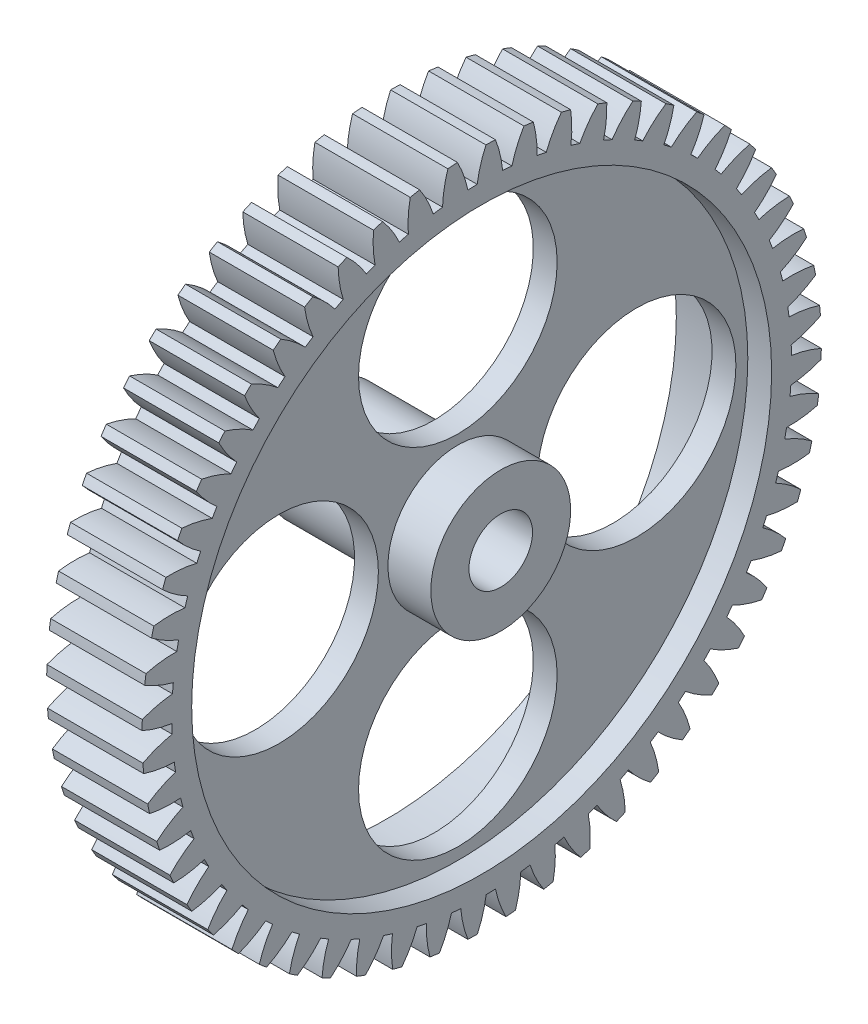
SolidWorks part; units mm, degrees
ref_plane "Front Plane" through (0, 0, 0) normal (0, 0, 1) x (1, 0, 0)
ref_plane "Top Plane" through (0, 0, 0) normal (0, 1, 0) x (1, 0, 0)
ref_plane "Right Plane" through (0, 0, 0) normal (1, 0, 0) x (0, 0, -1)
sketch "Sketch1" plane through (0, 0, 0) normal (1, 0, 0) x (0, 0, -1)
  line L0 (0, 0) -> (0.1063, 3.9986) construction
  line L1 (1.0369, 38.9862) -> (1.1366, 42.7349) construction
  circle A0 centre (0, 0) radius 42.75 construction
  circle A1 centre (0, 0) radius 41.375 construction
  circle A2 centre (0, 0) radius 39 construction
  circle A3 centre (0, 0) radius 4
  arc A4 (0, 41.375) -> (2.1992, 41.3165) centre (0, 0) cw
  arc A5 (-0.5634, 38.9959) -> (2.6354, 38.9109) centre (0, 0) cw
  arc A6 (0.5367, 42.7466) -> (1.7362, 42.7147) centre (0, 0) cw
  arc A7 (1.7362, 42.7147) -> (2.6354, 38.9109) centre (-11.2723, 37.6315) cw
  arc A8 (0.5367, 42.7466) -> (-0.5634, 38.9959) centre (13.2566, 36.9791) ccw
  arc A9 (5.3194, 42.4178) -> (3.8063, 38.8138) centre (17.3136, 35.2623) ccw
  arc A10 (3.8063, 38.8138) -> (6.9755, 38.3711) centre (0, 0) cw
  arc A11 (6.5078, 42.2518) -> (6.9755, 38.3711) centre (-6.988, 38.6569) cw
  arc A12 (5.3194, 42.4178) -> (6.5078, 42.2518) centre (0, 0) cw
  arc A13 (10.0352, 41.5555) -> (8.1281, 38.1436) centre (21.1529, 33.1021) ccw
  arc A14 (8.1281, 38.1436) -> (11.2278, 37.3488) centre (0, 0) cw
  arc A15 (11.1976, 41.2574) -> (11.2278, 37.3488) centre (-2.6159, 39.1963) cw
  arc A16 (10.0352, 41.5555) -> (11.1976, 41.2574) centre (0, 0) cw
  arc A17 (14.6249, 40.1706) -> (12.3477, 36.9937) centre (24.7261, 30.5256) ccw
  arc A18 (12.3477, 36.9937) -> (15.339, 35.8569) centre (0, 0) cw
  arc A19 (15.7466, 39.7443) -> (15.339, 35.8569) centre (1.7891, 39.2427) cw
  arc A20 (14.6249, 40.1706) -> (15.7466, 39.7443) centre (0, 0) cw
  arc A21 (19.0306, 38.2805) -> (16.412, 35.3786) centre (27.9884, 27.5652) ccw
  arc A22 (16.412, 35.3786) -> (19.2572, 33.914) centre (0, 0) cw
  arc A23 (20.0975, 37.7313) -> (19.2572, 33.914) centre (6.1717, 38.7956) cw
  arc A24 (19.0306, 38.2805) -> (20.0975, 37.7313) centre (0, 0) cw
  arc A25 (23.197, 35.9091) -> (20.27, 33.3186) centre (30.8988, 24.2582) ccw
  arc A26 (20.27, 33.3186) -> (22.9333, 31.5446) centre (0, 0) cw
  arc A27 (24.1957, 35.2439) -> (22.9333, 31.5446) centre (10.4766, 37.8607) cw
  arc A28 (23.197, 35.9091) -> (24.1957, 35.2439) centre (0, 0) cw
  arc A29 (27.0717, 33.0861) -> (23.873, 30.8396) centre (33.4205, 20.6461) ccw
  arc A30 (23.873, 30.8396) -> (26.321, 28.7786) centre (0, 0) cw
  arc A31 (27.9896, 32.3132) -> (26.321, 28.7786) centre (14.6498, 36.4496) cw
  arc A32 (27.0717, 33.0861) -> (27.9896, 32.3132) centre (0, 0) cw
  arc A33 (30.6059, 29.847) -> (27.1759, 27.9727) centre (35.522, 16.7743) ccw
  arc A34 (27.1759, 27.9727) -> (29.3777, 25.6506) centre (0, 0) cw
  arc A35 (31.4316, 28.9762) -> (29.3777, 25.6506) centre (18.6387, 34.5802) cw
  arc A36 (30.6059, 29.847) -> (31.4316, 28.9762) centre (0, 0) cw
  arc A37 (33.7553, 26.2325) -> (30.1369, 24.7541) centre (37.1768, 12.6917) ccw
  arc A38 (30.1369, 24.7541) -> (32.0649, 22.2001) centre (0, 0) cw
  arc A39 (34.4782, 25.2748) -> (32.0649, 22.2001) centre (22.3933, 32.2759) cw
  arc A40 (33.7553, 26.2325) -> (34.4782, 25.2748) centre (0, 0) cw
  arc A41 (36.4801, 22.2882) -> (32.719, 21.2242) centre (38.364, 8.4494) ccw
  arc A42 (32.719, 21.2242) -> (34.3489, 18.4703) centre (0, 0) cw
  arc A43 (37.0913, 21.2555) -> (34.3489, 18.4703) centre (25.8662, 29.5657) cw
  arc A44 (36.4801, 22.2882) -> (37.0913, 21.2555) centre (0, 0) cw
  arc A45 (38.7462, 18.0636) -> (34.8896, 17.4274) centre (39.0688, 4.1008) ccw
  arc A46 (34.8896, 17.4274) -> (36.2009, 14.5084) centre (0, 0) cw
  arc A47 (39.238, 16.9689) -> (36.2009, 14.5084) centre (29.0139, 26.4837) cw
  arc A48 (38.7462, 18.0636) -> (39.238, 16.9689) centre (0, 0) cw
  arc A49 (40.5251, 13.6118) -> (36.6215, 13.4114) centre (39.2823, -0.2993) ccw
  arc A50 (36.6215, 13.4114) -> (37.5977, 10.3639) centre (0, 0) cw
  arc A51 (40.8912, 12.469) -> (37.5977, 10.3639) centre (31.7967, 23.0686) cw
  arc A52 (40.5251, 13.6118) -> (40.8912, 12.469) centre (0, 0) cw
  arc A53 (41.7943, 8.9888) -> (37.8928, 9.2267) centre (39.0018, -4.6956) ccw
  arc A54 (37.8928, 9.2267) -> (38.5217, 6.0891) centre (0, 0) cw
  arc A55 (42.0301, 7.8122) -> (38.5217, 6.0891) centre (34.1796, 19.3635) cw
  arc A56 (41.7943, 8.9888) -> (42.0301, 7.8122) centre (0, 0) cw
  arc A57 (42.5379, 4.2528) -> (38.6876, 4.9261) centre (38.2309, -9.0329) ccw
  arc A58 (38.6876, 4.9261) -> (38.9613, 1.7378) centre (0, 0) cw
  arc A59 (42.6405, 3.0572) -> (38.9613, 1.7378) centre (36.1327, 15.4148) cw
  arc A60 (42.5379, 4.2528) -> (42.6405, 3.0572) centre (0, 0) cw
  arc A61 (42.7466, -0.5367) -> (38.9959, 0.5634) centre (36.9791, -13.2566) ccw
  arc A62 (38.9959, 0.5634) -> (38.9109, -2.6354) centre (0, 0) cw
  arc A63 (42.7147, -1.7362) -> (38.9109, -2.6354) centre (37.6315, 11.2723) cw
  arc A64 (42.7466, -0.5367) -> (42.7147, -1.7362) centre (0, 0) cw
  arc A65 (42.4178, -5.3194) -> (38.8138, -3.8063) centre (35.2623, -17.3136) ccw
  arc A66 (38.8138, -3.8063) -> (38.3711, -6.9755) centre (0, 0) cw
  arc A67 (42.2518, -6.5078) -> (38.3711, -6.9755) centre (38.6569, 6.988) cw
  arc A68 (42.4178, -5.3194) -> (42.2518, -6.5078) centre (0, 0) cw
  arc A69 (41.5555, -10.0352) -> (38.1436, -8.1281) centre (33.1021, -21.1529) ccw
  arc A70 (38.1436, -8.1281) -> (37.3488, -11.2278) centre (0, 0) cw
  arc A71 (41.2574, -11.1976) -> (37.3488, -11.2278) centre (39.1963, 2.6159) cw
  arc A72 (41.5555, -10.0352) -> (41.2574, -11.1976) centre (0, 0) cw
  arc A73 (40.1706, -14.6249) -> (36.9937, -12.3477) centre (30.5256, -24.7261) ccw
  arc A74 (36.9937, -12.3477) -> (35.8569, -15.339) centre (0, 0) cw
  arc A75 (39.7443, -15.7466) -> (35.8569, -15.339) centre (39.2427, -1.7891) cw
  arc A76 (40.1706, -14.6249) -> (39.7443, -15.7466) centre (0, 0) cw
  arc A77 (38.2805, -19.0306) -> (35.3786, -16.412) centre (27.5652, -27.9884) ccw
  arc A78 (35.3786, -16.412) -> (33.914, -19.2572) centre (0, 0) cw
  arc A79 (37.7313, -20.0975) -> (33.914, -19.2572) centre (38.7956, -6.1717) cw
  arc A80 (38.2805, -19.0306) -> (37.7313, -20.0975) centre (0, 0) cw
  arc A81 (35.9091, -23.197) -> (33.3186, -20.27) centre (24.2582, -30.8988) ccw
  arc A82 (33.3186, -20.27) -> (31.5446, -22.9333) centre (0, 0) cw
  arc A83 (35.2439, -24.1957) -> (31.5446, -22.9333) centre (37.8607, -10.4766) cw
  arc A84 (35.9091, -23.197) -> (35.2439, -24.1957) centre (0, 0) cw
  arc A85 (33.0861, -27.0717) -> (30.8396, -23.873) centre (20.6461, -33.4205) ccw
  arc A86 (30.8396, -23.873) -> (28.7786, -26.321) centre (0, 0) cw
  arc A87 (32.3132, -27.9896) -> (28.7786, -26.321) centre (36.4496, -14.6498) cw
  arc A88 (33.0861, -27.0717) -> (32.3132, -27.9896) centre (0, 0) cw
  arc A89 (29.847, -30.6059) -> (27.9727, -27.1759) centre (16.7743, -35.522) ccw
  arc A90 (27.9727, -27.1759) -> (25.6506, -29.3777) centre (0, 0) cw
  arc A91 (28.9762, -31.4316) -> (25.6506, -29.3777) centre (34.5802, -18.6387) cw
  arc A92 (29.847, -30.6059) -> (28.9762, -31.4316) centre (0, 0) cw
  arc A93 (26.2325, -33.7553) -> (24.7541, -30.1369) centre (12.6917, -37.1768) ccw
  arc A94 (24.7541, -30.1369) -> (22.2001, -32.0649) centre (0, 0) cw
  arc A95 (25.2748, -34.4782) -> (22.2001, -32.0649) centre (32.2759, -22.3933) cw
  arc A96 (26.2325, -33.7553) -> (25.2748, -34.4782) centre (0, 0) cw
  arc A97 (22.2882, -36.4801) -> (21.2242, -32.719) centre (8.4494, -38.364) ccw
  arc A98 (21.2242, -32.719) -> (18.4703, -34.3489) centre (0, 0) cw
  arc A99 (21.2555, -37.0913) -> (18.4703, -34.3489) centre (29.5657, -25.8662) cw
  arc A100 (22.2882, -36.4801) -> (21.2555, -37.0913) centre (0, 0) cw
  arc A101 (18.0636, -38.7462) -> (17.4274, -34.8896) centre (4.1008, -39.0688) ccw
  arc A102 (17.4274, -34.8896) -> (14.5084, -36.2009) centre (0, 0) cw
  arc A103 (16.9689, -39.238) -> (14.5084, -36.2009) centre (26.4837, -29.0139) cw
  arc A104 (18.0636, -38.7462) -> (16.9689, -39.238) centre (0, 0) cw
  arc A105 (13.6118, -40.5251) -> (13.4114, -36.6215) centre (-0.2993, -39.2823) ccw
  arc A106 (13.4114, -36.6215) -> (10.3639, -37.5977) centre (0, 0) cw
  arc A107 (12.469, -40.8912) -> (10.3639, -37.5977) centre (23.0686, -31.7967) cw
  arc A108 (13.6118, -40.5251) -> (12.469, -40.8912) centre (0, 0) cw
  arc A109 (8.9888, -41.7943) -> (9.2267, -37.8928) centre (-4.6956, -39.0018) ccw
  arc A110 (9.2267, -37.8928) -> (6.0891, -38.5217) centre (0, 0) cw
  arc A111 (7.8122, -42.0301) -> (6.0891, -38.5217) centre (19.3635, -34.1796) cw
  arc A112 (8.9888, -41.7943) -> (7.8122, -42.0301) centre (0, 0) cw
  arc A113 (4.2528, -42.5379) -> (4.9261, -38.6876) centre (-9.0329, -38.2309) ccw
  arc A114 (4.9261, -38.6876) -> (1.7378, -38.9613) centre (0, 0) cw
  arc A115 (3.0572, -42.6405) -> (1.7378, -38.9613) centre (15.4148, -36.1327) cw
  arc A116 (4.2528, -42.5379) -> (3.0572, -42.6405) centre (0, 0) cw
  arc A117 (-0.5367, -42.7466) -> (0.5634, -38.9959) centre (-13.2566, -36.9791) ccw
  arc A118 (0.5634, -38.9959) -> (-2.6354, -38.9109) centre (0, 0) cw
  arc A119 (-1.7362, -42.7147) -> (-2.6354, -38.9109) centre (11.2723, -37.6315) cw
  arc A120 (-0.5367, -42.7466) -> (-1.7362, -42.7147) centre (0, 0) cw
  arc A121 (-5.3194, -42.4178) -> (-3.8063, -38.8138) centre (-17.3136, -35.2623) ccw
  arc A122 (-3.8063, -38.8138) -> (-6.9755, -38.3711) centre (0, 0) cw
  arc A123 (-6.5078, -42.2518) -> (-6.9755, -38.3711) centre (6.988, -38.6569) cw
  arc A124 (-5.3194, -42.4178) -> (-6.5078, -42.2518) centre (0, 0) cw
  arc A125 (-10.0352, -41.5555) -> (-8.1281, -38.1436) centre (-21.1529, -33.1021) ccw
  arc A126 (-8.1281, -38.1436) -> (-11.2278, -37.3488) centre (0, 0) cw
  arc A127 (-11.1976, -41.2574) -> (-11.2278, -37.3488) centre (2.6159, -39.1963) cw
  arc A128 (-10.0352, -41.5555) -> (-11.1976, -41.2574) centre (0, 0) cw
  arc A129 (-14.6249, -40.1706) -> (-12.3477, -36.9937) centre (-24.7261, -30.5256) ccw
  arc A130 (-12.3477, -36.9937) -> (-15.339, -35.8569) centre (0, 0) cw
  arc A131 (-15.7466, -39.7443) -> (-15.339, -35.8569) centre (-1.7891, -39.2427) cw
  arc A132 (-14.6249, -40.1706) -> (-15.7466, -39.7443) centre (0, 0) cw
  arc A133 (-19.0306, -38.2805) -> (-16.412, -35.3786) centre (-27.9884, -27.5652) ccw
  arc A134 (-16.412, -35.3786) -> (-19.2572, -33.914) centre (0, 0) cw
  arc A135 (-20.0975, -37.7313) -> (-19.2572, -33.914) centre (-6.1717, -38.7956) cw
  arc A136 (-19.0306, -38.2805) -> (-20.0975, -37.7313) centre (0, 0) cw
  arc A137 (-23.197, -35.9091) -> (-20.27, -33.3186) centre (-30.8988, -24.2582) ccw
  arc A138 (-20.27, -33.3186) -> (-22.9333, -31.5446) centre (0, 0) cw
  arc A139 (-24.1957, -35.2439) -> (-22.9333, -31.5446) centre (-10.4766, -37.8607) cw
  arc A140 (-23.197, -35.9091) -> (-24.1957, -35.2439) centre (0, 0) cw
  arc A141 (-27.0717, -33.0861) -> (-23.873, -30.8396) centre (-33.4205, -20.6461) ccw
  arc A142 (-23.873, -30.8396) -> (-26.321, -28.7786) centre (0, 0) cw
  arc A143 (-27.9896, -32.3132) -> (-26.321, -28.7786) centre (-14.6498, -36.4496) cw
  arc A144 (-27.0717, -33.0861) -> (-27.9896, -32.3132) centre (0, 0) cw
  arc A145 (-30.6059, -29.847) -> (-27.1759, -27.9727) centre (-35.522, -16.7743) ccw
  arc A146 (-27.1759, -27.9727) -> (-29.3777, -25.6506) centre (0, 0) cw
  arc A147 (-31.4316, -28.9762) -> (-29.3777, -25.6506) centre (-18.6387, -34.5802) cw
  arc A148 (-30.6059, -29.847) -> (-31.4316, -28.9762) centre (0, 0) cw
  arc A149 (-33.7553, -26.2325) -> (-30.1369, -24.7541) centre (-37.1768, -12.6917) ccw
  arc A150 (-30.1369, -24.7541) -> (-32.0649, -22.2001) centre (0, 0) cw
  arc A151 (-34.4782, -25.2748) -> (-32.0649, -22.2001) centre (-22.3933, -32.2759) cw
  arc A152 (-33.7553, -26.2325) -> (-34.4782, -25.2748) centre (0, 0) cw
  arc A153 (-36.4801, -22.2882) -> (-32.719, -21.2242) centre (-38.364, -8.4494) ccw
  arc A154 (-32.719, -21.2242) -> (-34.3489, -18.4703) centre (0, 0) cw
  arc A155 (-37.0913, -21.2555) -> (-34.3489, -18.4703) centre (-25.8662, -29.5657) cw
  arc A156 (-36.4801, -22.2882) -> (-37.0913, -21.2555) centre (0, 0) cw
  arc A157 (-38.7462, -18.0636) -> (-34.8896, -17.4274) centre (-39.0688, -4.1008) ccw
  arc A158 (-34.8896, -17.4274) -> (-36.2009, -14.5084) centre (0, 0) cw
  arc A159 (-39.238, -16.9689) -> (-36.2009, -14.5084) centre (-29.0139, -26.4837) cw
  arc A160 (-38.7462, -18.0636) -> (-39.238, -16.9689) centre (0, 0) cw
  arc A161 (-40.5251, -13.6118) -> (-36.6215, -13.4114) centre (-39.2823, 0.2993) ccw
  arc A162 (-36.6215, -13.4114) -> (-37.5977, -10.3639) centre (0, 0) cw
  arc A163 (-40.8912, -12.469) -> (-37.5977, -10.3639) centre (-31.7967, -23.0686) cw
  arc A164 (-40.5251, -13.6118) -> (-40.8912, -12.469) centre (0, 0) cw
  arc A165 (-41.7943, -8.9888) -> (-37.8928, -9.2267) centre (-39.0018, 4.6956) ccw
  arc A166 (-37.8928, -9.2267) -> (-38.5217, -6.0891) centre (0, 0) cw
  arc A167 (-42.0301, -7.8122) -> (-38.5217, -6.0891) centre (-34.1796, -19.3635) cw
  arc A168 (-41.7943, -8.9888) -> (-42.0301, -7.8122) centre (0, 0) cw
  arc A169 (-42.5379, -4.2528) -> (-38.6876, -4.9261) centre (-38.2309, 9.0329) ccw
  arc A170 (-38.6876, -4.9261) -> (-38.9613, -1.7378) centre (0, 0) cw
  arc A171 (-42.6405, -3.0572) -> (-38.9613, -1.7378) centre (-36.1327, -15.4148) cw
  arc A172 (-42.5379, -4.2528) -> (-42.6405, -3.0572) centre (0, 0) cw
  arc A173 (-42.7466, 0.5367) -> (-38.9959, -0.5634) centre (-36.9791, 13.2566) ccw
  arc A174 (-38.9959, -0.5634) -> (-38.9109, 2.6354) centre (0, 0) cw
  arc A175 (-42.7147, 1.7362) -> (-38.9109, 2.6354) centre (-37.6315, -11.2723) cw
  arc A176 (-42.7466, 0.5367) -> (-42.7147, 1.7362) centre (0, 0) cw
  arc A177 (-42.4178, 5.3194) -> (-38.8138, 3.8063) centre (-35.2623, 17.3136) ccw
  arc A178 (-38.8138, 3.8063) -> (-38.3711, 6.9755) centre (0, 0) cw
  arc A179 (-42.2518, 6.5078) -> (-38.3711, 6.9755) centre (-38.6569, -6.988) cw
  arc A180 (-42.4178, 5.3194) -> (-42.2518, 6.5078) centre (0, 0) cw
  arc A181 (-41.5555, 10.0352) -> (-38.1436, 8.1281) centre (-33.1021, 21.1529) ccw
  arc A182 (-38.1436, 8.1281) -> (-37.3488, 11.2278) centre (0, 0) cw
  arc A183 (-41.2574, 11.1976) -> (-37.3488, 11.2278) centre (-39.1963, -2.6159) cw
  arc A184 (-41.5555, 10.0352) -> (-41.2574, 11.1976) centre (0, 0) cw
  arc A185 (-40.1706, 14.6249) -> (-36.9937, 12.3477) centre (-30.5256, 24.7261) ccw
  arc A186 (-36.9937, 12.3477) -> (-35.8569, 15.339) centre (0, 0) cw
  arc A187 (-39.7443, 15.7466) -> (-35.8569, 15.339) centre (-39.2427, 1.7891) cw
  arc A188 (-40.1706, 14.6249) -> (-39.7443, 15.7466) centre (0, 0) cw
  arc A189 (-38.2805, 19.0306) -> (-35.3786, 16.412) centre (-27.5652, 27.9884) ccw
  arc A190 (-35.3786, 16.412) -> (-33.914, 19.2572) centre (0, 0) cw
  arc A191 (-37.7313, 20.0975) -> (-33.914, 19.2572) centre (-38.7956, 6.1717) cw
  arc A192 (-38.2805, 19.0306) -> (-37.7313, 20.0975) centre (0, 0) cw
  arc A193 (-35.9091, 23.197) -> (-33.3186, 20.27) centre (-24.2582, 30.8988) ccw
  arc A194 (-33.3186, 20.27) -> (-31.5446, 22.9333) centre (0, 0) cw
  arc A195 (-35.2439, 24.1957) -> (-31.5446, 22.9333) centre (-37.8607, 10.4766) cw
  arc A196 (-35.9091, 23.197) -> (-35.2439, 24.1957) centre (0, 0) cw
  arc A197 (-33.0861, 27.0717) -> (-30.8396, 23.873) centre (-20.6461, 33.4205) ccw
  arc A198 (-30.8396, 23.873) -> (-28.7786, 26.321) centre (0, 0) cw
  arc A199 (-32.3132, 27.9896) -> (-28.7786, 26.321) centre (-36.4496, 14.6498) cw
  arc A200 (-33.0861, 27.0717) -> (-32.3132, 27.9896) centre (0, 0) cw
  arc A201 (-29.847, 30.6059) -> (-27.9727, 27.1759) centre (-16.7743, 35.522) ccw
  arc A202 (-27.9727, 27.1759) -> (-25.6506, 29.3777) centre (0, 0) cw
  arc A203 (-28.9762, 31.4316) -> (-25.6506, 29.3777) centre (-34.5802, 18.6387) cw
  arc A204 (-29.847, 30.6059) -> (-28.9762, 31.4316) centre (0, 0) cw
  arc A205 (-26.2325, 33.7553) -> (-24.7541, 30.1369) centre (-12.6917, 37.1768) ccw
  arc A206 (-24.7541, 30.1369) -> (-22.2001, 32.0649) centre (0, 0) cw
  arc A207 (-25.2748, 34.4782) -> (-22.2001, 32.0649) centre (-32.2759, 22.3933) cw
  arc A208 (-26.2325, 33.7553) -> (-25.2748, 34.4782) centre (0, 0) cw
  arc A209 (-22.2882, 36.4801) -> (-21.2242, 32.719) centre (-8.4494, 38.364) ccw
  arc A210 (-21.2242, 32.719) -> (-18.4703, 34.3489) centre (0, 0) cw
  arc A211 (-21.2555, 37.0913) -> (-18.4703, 34.3489) centre (-29.5657, 25.8662) cw
  arc A212 (-22.2882, 36.4801) -> (-21.2555, 37.0913) centre (0, 0) cw
  arc A213 (-18.0636, 38.7462) -> (-17.4274, 34.8896) centre (-4.1008, 39.0688) ccw
  arc A214 (-17.4274, 34.8896) -> (-14.5084, 36.2009) centre (0, 0) cw
  arc A215 (-16.9689, 39.238) -> (-14.5084, 36.2009) centre (-26.4837, 29.0139) cw
  arc A216 (-18.0636, 38.7462) -> (-16.9689, 39.238) centre (0, 0) cw
  arc A217 (-13.6118, 40.5251) -> (-13.4114, 36.6215) centre (0.2993, 39.2823) ccw
  arc A218 (-13.4114, 36.6215) -> (-10.3639, 37.5977) centre (0, 0) cw
  arc A219 (-12.469, 40.8912) -> (-10.3639, 37.5977) centre (-23.0686, 31.7967) cw
  arc A220 (-13.6118, 40.5251) -> (-12.469, 40.8912) centre (0, 0) cw
  arc A221 (-8.9888, 41.7943) -> (-9.2267, 37.8928) centre (4.6956, 39.0018) ccw
  arc A222 (-9.2267, 37.8928) -> (-6.0891, 38.5217) centre (0, 0) cw
  arc A223 (-7.8122, 42.0301) -> (-6.0891, 38.5217) centre (-19.3635, 34.1796) cw
  arc A224 (-8.9888, 41.7943) -> (-7.8122, 42.0301) centre (0, 0) cw
  arc A225 (-4.2528, 42.5379) -> (-4.9261, 38.6876) centre (9.0329, 38.2309) ccw
  arc A226 (-4.9261, 38.6876) -> (-1.7378, 38.9613) centre (0, 0) cw
  arc A227 (-3.0572, 42.6405) -> (-1.7378, 38.9613) centre (-15.4148, 36.1327) cw
  arc A228 (-4.2528, 42.5379) -> (-3.0572, 42.6405) centre (0, 0) cw
  circle A229 centre (0, 0) radius 39
  circle A230 centre (0, 0) radius 22.5 construction
  circle A231 centre (0, 22.5) radius 12.5
  circle A234 centre (22.5, 0) radius 12.5
  circle A235 centre (0, -22.5) radius 12.5
  circle A236 centre (-22.5, 0) radius 12.5
  point P13 (1.0369, 38.9862)
  point P16 (1.1366, 42.7349)
  point P351 (0, 0)
  point P360 (0, 0)
  point P364 (0, 0)
  dimension "D1" = 85.5
  dimension "D2" = 82.75
  dimension "D3" = 78
  dimension "D4" = 8
  dimension "D5" = 2.2
  dimension "D6" = 3.2
  dimension "D7" = 1.2
  dimension "D8" = 56
extrude "Boss-Extrude1" add sketch "Sketch1" along normal blind 12 contours A62 A229 A58 A54 A50 A46 A42 A38 A34 A30 A26 A22 A18 A14 A10 A5 A226 A222 A218 A214 A210 A206 A202 A198 A194 A190 A186 | A144 A141 A142 A143 | A140 A137 A138 A139 | A136 A133 A134 A135 | A132 A129 A130 A131 | A128 A125 A126 A127 | A124 A121 A122 A123 | A120 A117 A118 A119 | A116 A113 A114 A115 | A112 A109 A110 A111 | A108 A105 A106 A107 | A104 A101 A102 A103 | A100 A97 A98 A99 | A96 A93 A94 A95 | A92 A89 A90 A91 | A88 A85 A86 A87 | A84 A81 A82 A83 | A148 A145 A146 A147 | A152 A149 A150 A151 | A156 A153 A154 A155 | A160 A157 A158 A159 | A164 A161 A162 A163 | A168 A165 A166 A167 | A172 A169 A170 A171 | A176 A173 A174 A175 | A180 A177 A178 A179 | A184 A181 A182 A183 | A60 A57 A58 A59 | A64 A61 A62 A63 | A68 A65 A66 A67 | A72 A69 A70 A71 | A76 A73 A74 A75 | A80 A77 A78 A79 | A188 A185 A186 A187 | A192 A189 A190 A191 | A196 A193 A194 A195 | A200 A197 A198 A199 | A204 A201 A202 A203 | A208 A205 A206 A207 | A212 A209 A210 A211 | A216 A213 A214 A215 | A220 A217 A218 A219 | A224 A221 A222 A223 | A228 A225 A226 A227 | A12 A9 A10 A11 | A16 A13 A14 A15 | A20 A17 A18 A19 | A56 A53 A54 A55 | A52 A49 A50 A51 | A48 A45 A46 A47 | A44 A41 A42 A43 | A40 A37 A38 A39 | A36 A33 A34 A35 | A32 A29 A30 A31 | A28 A25 A26 A27 | A24 A21 A22 A23 | A6 A8 A4 A7 | A4 A8 A5 A7 region at (0, 41.9781, -1.1164) region at (0, 40.0938, -1.0663) region at (0, 37.8835, -1.0075) region at (0, 40.4588, 3.4722) region at (0, 40.217, -5.6178) region at (0, 39.8156, 7.9803) region at (0, 39.3351, -10.0853) region at (0, 38.6717, 12.388) region at (0, 37.9586, -14.4261) region at (0, 37.0416, 16.64) region at (0, 36.1047, -18.5854) region at (0, 34.9456, 20.6827) region at (0, 33.7968, -22.511) region at (0, 32.4101, 24.4653) region at (0, 31.0639, -26.1535) region at (0, 29.4671, 27.9403) region at (0, 27.9403, -29.4671) region at (0, 26.1535, 31.0639) region at (0, 24.4653, -32.4101) region at (0, 22.511, 33.7968) region at (0, 20.6827, -34.9456) region at (0, 18.5854, 36.1047) region at (0, 16.64, -37.0416) region at (0, 14.4261, 37.9586) region at (0, 12.388, -38.6717) region at (0, 10.0853, 39.3351) region at (0, 7.9803, -39.8156) region at (0, 5.6178, 40.217) region at (0, 3.4722, -40.4588) region at (0, 1.0796, 40.5931) region at (0, -1.0796, -40.5931) region at (0, -3.4722, 40.4588) region at (0, -5.6178, -40.217) region at (0, -7.9803, 39.8156) region at (0, -10.0853, -39.3351) region at (0, -12.388, 38.6717) region at (0, -14.4261, -37.9586) region at (0, -16.64, 37.0416) region at (0, -18.5854, -36.1047) region at (0, -20.6827, 34.9456) region at (0, -22.511, -33.7968) region at (0, -24.4653, 32.4101) region at (0, -26.1535, -31.0639) region at (0, -27.9403, 29.4671) region at (0, -29.4671, -27.9403) region at (0, -31.0639, 26.1535) region at (0, -32.4101, -24.4653) region at (0, -33.7968, 22.511) region at (0, -34.9456, -20.6827) region at (0, -36.1047, 18.5854) region at (0, -37.0416, -16.64) region at (0, -37.9586, 14.4261) region at (0, -38.6717, -12.388) region at (0, -39.3351, 10.0853) region at (0, -39.8156, -7.9803) region at (0, -40.217, 5.6178) region at (0, -40.4588, -3.4722) region at (0, -40.5931, 1.0796)
sketch "Sketch4" plane through (12, 0, 0) normal (1, 0, 0) x (0, 0, -1)
  circle A0 centre (0, 0) radius 36.5
extrude "Cut-Extrude1" cut sketch "Sketch4" against normal blind 3
sketch "Sketch5" plane through (0, 0, 0) normal (-1, 0, 0) x (0, 0, 1)
  circle A0 centre (0, 0) radius 36.5
extrude "Cut-Extrude2" cut sketch "Sketch5" against normal blind 6
sketch "Sketch6" plane through (9, 0, 0) normal (1, 0, 0) x (0, 0, -1)
  circle A0 centre (0, 0) radius 8.8
  circle A1 centre (0, 0) radius 4
  dimension "D1" = 17.6
extrude "Boss-Extrude2" add sketch "Sketch6" along normal blind 5.4
sketch "Sketch7" plane through (6, 0, 0) normal (-1, 0, 0) x (0, 0, 1)
  circle A0 centre (0, 0) radius 4
  circle A1 centre (0, 0) radius 7.2
extrude "Boss-Extrude3" add sketch "Sketch7" along normal blind 13.5
